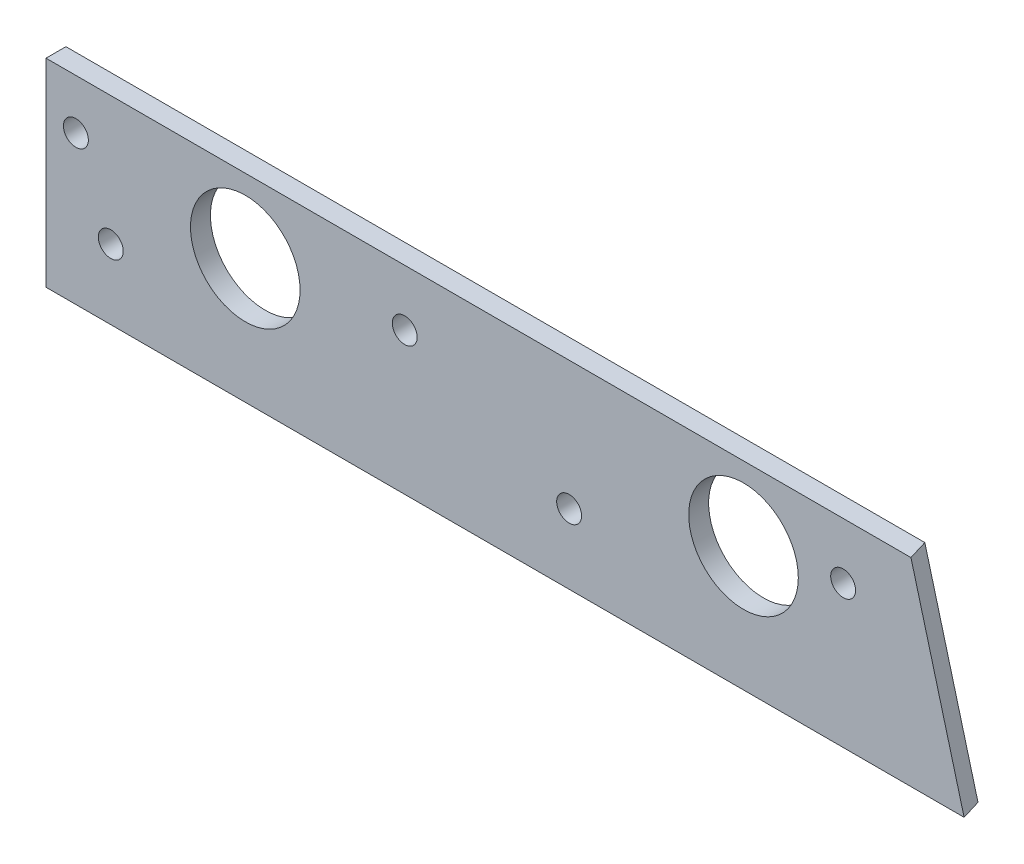
SolidWorks part; units mm, degrees
ref_plane "Front Plane" through (0, 0, 0) normal (0, 0, 1) x (1, 0, 0)
ref_plane "Top Plane" through (0, 0, 0) normal (0, 1, 0) x (1, 0, 0)
ref_plane "Right Plane" through (0, 0, 0) normal (1, 0, 0) x (0, 0, -1)
sketch "Sketch2" plane through (0, 0, 0) normal (0, 0, 1) x (1, 0, 0)
  line L0 (80.1381, -30) -> (69.4674, 9.8235)
  line L1 (-105, -30) -> (80.1381, -30)
  line L2 (-105, -30) -> (-105, 9.8235)
  line L7 (69.4674, 9.8235) -> (-105, 9.8235)
  circle A0 centre (35, -5) radius 11
  circle A1 centre (-65, -5) radius 11
  circle A2 centre (-92, -16) radius 2.5
  circle A3 centre (0, -16) radius 2.5
  circle A4 centre (-99, -0.1765) radius 2.5
  circle A5 centre (-33, -1.4532) radius 2.5
  circle A6 centre (55, -1.4532) radius 2.5
  point P0 (0, 0)
  dimension "D6" = 22
  dimension "D7" = 22
  dimension "D8" = 5
  dimension "D9" = 5
  dimension "D10" = 14
  dimension "D2" = 15
  dimension "D3" = 40
  dimension "D4" = 10
  dimension "D5" = 25
  dimension "D11" = 13
  dimension "D12" = 14
  dimension "D13" = 72
  dimension "D14" = 160
  dimension "D15" = 6
extrude "Boss-Extrude1" add sketch "Sketch2" along normal blind 4
chamfer "Chamfer1" distance 2 angle 73.67 1 edges at (74.8027, -10.0883, 0) first distance on face at (-30.5, -1.4532, 0)
